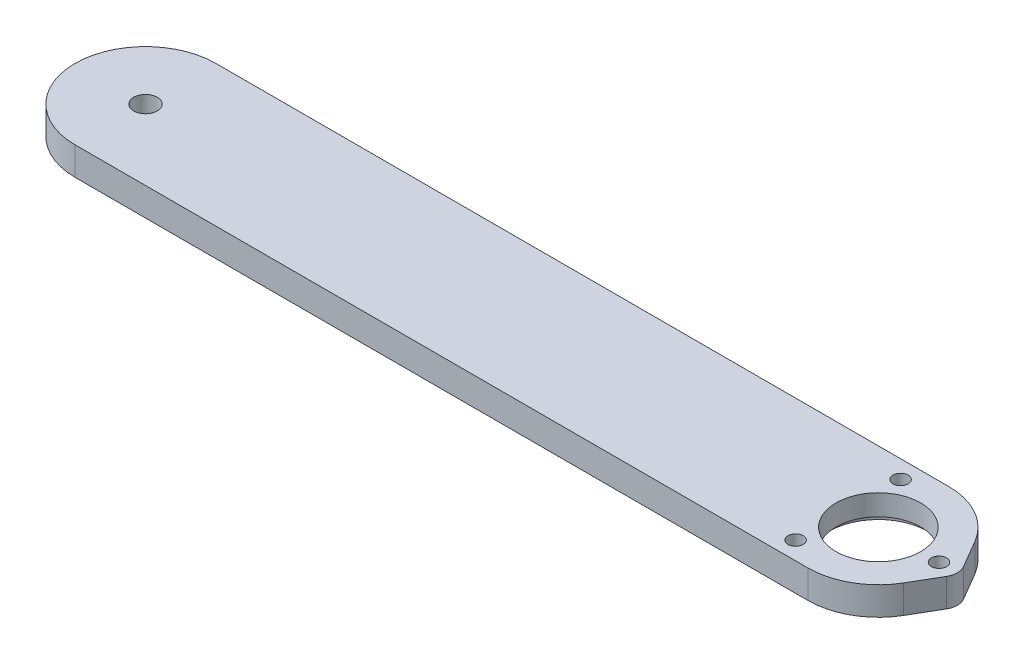
SolidWorks part; units mm, degrees
ref_plane "前视基准面" through (0, 0, 0) normal (0, 0, 1) x (1, 0, 0)
ref_plane "上视基准面" through (0, 0, 0) normal (0, 1, 0) x (1, 0, 0)
ref_plane "右视基准面" through (0, 0, 0) normal (1, 0, 0) x (0, 0, -1)
sketch "草图1" plane through (0, 0, 0) normal (0, 1, 0) x (1, 0, 0)
  line L0 (-65, 0) -> (65, 0) construction
  line L1 (-65, 12.5) -> (65, 12.5)
  line L2 (-65, -12.5) -> (65, -12.5)
  arc A0 (-65, 12.5) -> (-65, -12.5) centre (-65, 0) ccw
  arc A1 (65, -12.5) -> (65, 12.5) centre (65, 0) ccw
  point P2 (0, 0)
  dimension "D2" = 12.5
  dimension "D1" = 130
extrude "凸台-拉伸1" add sketch "草图1" along normal blind 5
sketch "草图10" plane through (0, 0, 0) normal (0, -1, 0) x (1, 0, 0)
  line L0 (75.7955, -6.3014) -> (78.5909, -1.5123)
  line L3 (75.7955, 6.3014) -> (78.5909, 1.5123)
  line L4 (75.7955, -6.3014) -> (75.7955, 6.3014)
  line L5 (76, 0) -> (77.5, 0) construction
  circle A5 centre (76, 0) radius 3 construction
  arc A6 (65, -12.5) -> (65, 12.5) centre (65, 0) ccw construction
  arc A7 (78.5909, -1.5123) -> (78.5909, 1.5123) centre (76, 0) ccw
  dimension "D1" = 6
  dimension "D2" = 1.5
extrude "凸台-拉伸5" add sketch "草图10" against normal up to surface (5 mm away) up to face at (0, 5, 0)
sketch "草图7" plane through (0, 5, 0) normal (0, 1, 0) x (1, 0, 0)
  circle A0 centre (65, 0) radius 7.5
  dimension "D1" = 15
extrude "切除-拉伸2" cut sketch "草图7" against normal up to next
sketch "草图8" plane through (0, 0, 0) normal (0, 1, 0) x (1, 0, 0)
  circle A0 centre (65, 0) radius 8.75
  dimension "D1" = 17.5
extrude "切除-拉伸3" cut sketch "草图8" along normal blind 1.3
sketch "草图9" plane through (0, 0, 0) normal (0, -1, 0) x (1, 0, 0)
  line L0 (65, 0) -> (54.25, 0) construction
  line L1 (65, 0) -> (59.625, 9.3098) construction
  circle A0 centre (65, 0) radius 10.75 construction
  circle A5 centre (59.625, 9.3098) radius 1.35
  circle A9 centre (75.75, 0) radius 1.35
  circle A10 centre (59.625, -9.3098) radius 1.35
  point P12 (65, 0)
  point P15 (65, 0)
  dimension "22" = 21.5
  dimension "D3" = 2.7
  dimension "D2" = 60
  dimension "D1" = 3
extrude "切除-拉伸4" cut sketch "草图9" against normal up to next
sketch "草图12" plane through (0, 5, 0) normal (0, 1, 0) x (1, 0, 0)
  circle A0 centre (-65, 0) radius 2.1
  dimension "D1" = 4.2
extrude "切除-拉伸5" cut sketch "草图12" against normal up to next
sketch "草图13" plane through (0, 0, 0) normal (0, -1, 0) x (1, 0, 0)
  circle A0 centre (59.625, 9.3098) radius 2.75
  circle A1 centre (75.75, 0) radius 2.75
  circle A2 centre (59.625, -9.3098) radius 2.75
  dimension "D1" = 5.5
sketch "草图14" plane through (0, 0, 0) normal (0, -1, 0) x (1, 0, 0)
  line L0 (65, -12.5) -> (-65, -12.5) construction
  line L1 (-52, -12.5) -> (-12, -12.5)
  line L2 (-52, -12.5) -> (-52, -5.5)
  line L3 (-52, -5.5) -> (-12, -5.5)
  line L4 (-12, -12.5) -> (-12, -5.5)
  dimension "D1" = 7
  dimension "D2" = 40
  dimension "D3" = 13
extrude "凸台-拉伸6" add sketch "草图14" along normal blind 15
chamfer "倒角1" distance 7 distance2 3 1 edges at (-52, -7.5, -5.5) first distance on face at (-32, -7.5, -5.5)
sketch "草图15" plane through (-52, 0, 0) normal (-1, 0, 0) x (0, 0, 1)
  line L0 (-5.5, -12.5) -> (-4.5, -12.5) construction
  line L1 (-5.5, 0) -> (-5.5, -15) construction
  line L2 (-5.5, -15) -> (-8.5, -15) construction
  circle A0 centre (-4.5, -12.5) radius 2
  dimension "D2" = 4
  dimension "D1" = 1
  dimension "D3" = 2.5
extrude "切除-拉伸6" cut sketch "草图15" against normal up to next
fillet "圆角3" radius 2 6 edges at (-52, -7.5, -8.5) (-52, -7.5, -12.5) (-45, -14.616, -5.5) (-45, -5.384, -5.5) (-12, -5.384, -5.5) (-12, -7.5, -12.5)
chamfer "倒角2" distance 5 angle 45 9 edges at (-51.4142, 0, -11.9142) (-52, 0, -10.1594) (-12.5858, 0, -11.9142) (-51.6697, 0, -8.7178) (-12, 0, -9) (-48.0826, 0, -6.8211) (-12.5858, 0, -6.0858) (-44.9916, 0, -5.5408) (-29.2947, 0, -5.5)
sketch "草图16" plane through (0, -15, 0) normal (0, -1, 0) x (1, 0, 0)
  line L0 (-61.3333, -12.5) -> (-33.3333, -0.5)
  line L1 (-56.7082, -12.5) -> (-65, -12.5) construction
  line L2 (-44.5895, -0.5) -> (-14, -0.5) construction
  line L3 (-33.3333, -0.5) -> (-61.3333, -0.5)
  line L4 (-61.3333, -0.5) -> (-61.3333, -12.5)
  line L5 (-45.3773, -5.6617) -> (-50.7878, -7.9805) construction
extrude "切除-拉伸7" cut sketch "草图16" against normal up to surface (15 mm away) up to face at (-2.8835, 0, -3.698)
sketch "草图17" plane through (0, 0, 0) normal (0, -1, 0) x (1, 0, 0)
  circle A0 centre (-65, 0) radius 2.1
  circle A1 centre (-65, 0) radius 7.5
  circle A2 centre (-65, 0) radius 2.1 construction
  dimension "D1" = 15
extrude "凸台-拉伸7" add sketch "草图17" along normal blind 2
chamfer "倒角3" distance 2 angle 45 1 edges at (-65, -2, -7.5)
